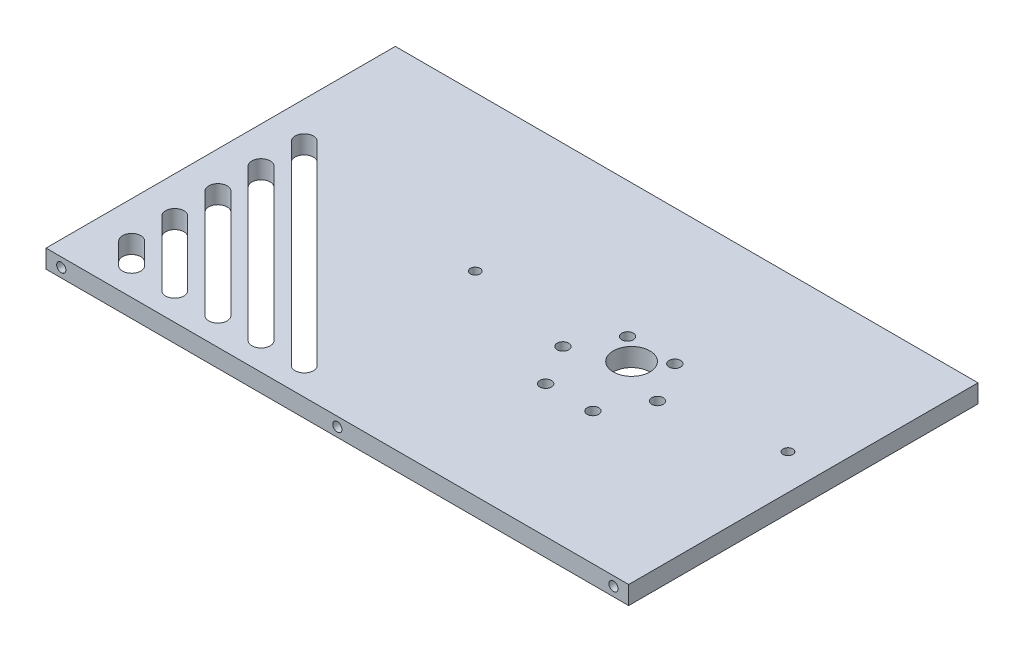
SolidWorks part; units mm, degrees
ref_plane "Front Plane" through (0, 0, 0) normal (1, 0, 0) x (0, 1, 0)
ref_plane "Top Plane" through (0, 0, 0) normal (0, 0, 1) x (0, 1, 0)
ref_plane "Right Plane" through (0, 0, 0) normal (0, 1, 0) x (-1, 0, 0)
sketch "Sketch1" plane through (0, 0, 0) normal (0, 1, 0) x (-1, 0, 0)
  line L3 (191, 0) -> (0, 0)
  line L10 (0, 114.5) -> (191, 114.5)
  line L15 (191, 114.5) -> (191, 0)
  line L17 (0, 114.5) -> (0, 0)
  point P16 (-5.5507, 58)
  point P19 (0, 0)
  point P27 (191, 0)
  dimension "D1" = 191
  dimension "D3" = 114.5
extrude "Boss-Extrude1" add sketch "Sketch1" along normal blind 6 contours L10 L17 L3 L15 region at (-95.5, 0, 57.25)
sketch "Sketch2" plane through (0, 0, 0) normal (0, -1, 0) x (1, 0, 0)
  line L0 (-113.4294, 6) -> (27.4505, 6) construction
  line L1 (-153.4835, 108.5) -> (20.1803, 108.5) construction
  line L2 (-48.0825, 39.2019) -> (29.2007, 39.2019) construction
  line L3 (-81.35, 53.663) -> (-81.35, 63.7746) construction
  line L4 (-191, 114.5) -> (-191, 0) construction
  line L7 (-44.35, 45.4394) -> (-44.35, 50045.4394) construction
  line L8 (-10, 10.8138) -> (-10, 44.7981) construction
  line L9 (-179, 84.2868) -> (-157.7868, 105.5) construction
  line L10 (-181.1213, 86.4081) -> (-159.9081, 107.6213)
  line L11 (-176.8787, 82.1655) -> (-155.6655, 103.3787)
  line L12 (-179, 70.1447) -> (-143.6447, 105.5) construction
  line L13 (-181.1213, 72.266) -> (-145.766, 107.6213)
  line L14 (-176.8787, 68.0233) -> (-141.5233, 103.3787)
  line L15 (-179, 56.0025) -> (-129.5025, 105.5) construction
  line L16 (-181.1213, 58.1238) -> (-131.6238, 107.6213)
  line L17 (-176.8787, 53.8812) -> (-127.3812, 103.3787)
  line L18 (-179, 41.8604) -> (-115.3604, 105.5) construction
  line L19 (-181.1213, 43.9817) -> (-117.4817, 107.6213)
  line L20 (-176.8787, 39.7391) -> (-113.2391, 103.3787)
  line L21 (-182, 120.5517) -> (-182, 16.1068) construction
  line L23 (-62.85, -5.1417) -> (-62.85, -109.5866) construction
  line L24 (-179, 98.4289) -> (-171.9289, 105.5) construction
  line L25 (-166.2721, 92.7721) -> (-163.4437, 89.9437) construction
  line L26 (-159.201, 85.701) -> (-156.3726, 82.8726) construction
  line L27 (-152.1299, 78.6299) -> (-149.3015, 75.8015) construction
  line L28 (-181.1213, 100.5503) -> (-174.0503, 107.6213)
  line L29 (-176.8787, 96.3076) -> (-169.8076, 103.3787)
  line L30 (-170.5147, 97.0147) -> (-173.3431, 99.8431) construction
  line L32 (-191, 0) -> (0, 0) construction
  line L33 (-62.85, 57.7019) -> (-62.85, -1.2686) construction
  line L35 (0, 114.5) -> (-191, 114.5) construction
  line L36 (0, 114.5) -> (0, 0) construction
  circle A7 centre (-62.85, 50.7019) radius 6
  circle A9 centre (-62.85, 57.7019) radius 18.5 construction
  arc A11 (-181.1213, 86.4081) -> (-176.8787, 82.1655) centre (-179, 84.2868) ccw
  arc A12 (-155.6655, 103.3787) -> (-159.9081, 107.6213) centre (-157.7868, 105.5) ccw
  arc A13 (-181.1213, 72.266) -> (-176.8787, 68.0233) centre (-179, 70.1447) ccw
  arc A14 (-141.5233, 103.3787) -> (-145.766, 107.6213) centre (-143.6447, 105.5) ccw
  arc A15 (-181.1213, 58.1238) -> (-176.8787, 53.8812) centre (-179, 56.0025) ccw
  arc A16 (-127.3812, 103.3787) -> (-131.6238, 107.6213) centre (-129.5025, 105.5) ccw
  arc A17 (-181.1213, 43.9817) -> (-176.8787, 39.7391) centre (-179, 41.8604) ccw
  arc A18 (-113.2391, 103.3787) -> (-117.4817, 107.6213) centre (-115.3604, 105.5) ccw
  arc A19 (-181.1213, 100.5503) -> (-176.8787, 96.3076) centre (-179, 98.4289) ccw
  arc A20 (-169.8076, 103.3787) -> (-174.0503, 107.6213) centre (-171.9289, 105.5) ccw
  circle A21 centre (-62.85, 57.7019) radius 15.5 construction
  circle A22 centre (-78.35, 57.7019) radius 1.9
  circle A23 centre (-70.6, 71.1253) radius 1.9
  circle A24 centre (-55.1, 71.1253) radius 1.9
  circle A25 centre (-47.35, 57.7019) radius 1.9
  circle A26 centre (-55.1, 44.2785) radius 1.9
  circle A27 centre (-70.6, 44.2785) radius 1.9
  circle A32 centre (-62.85, 50.7019) radius 51.25 construction
  circle A33 centre (-114.1, 50.7019) radius 1.6
  circle A34 centre (-62.85, 101.9519) radius 1.6 construction
  circle A35 centre (-11.6, 50.7019) radius 1.6
  circle A36 centre (-62.85, -0.5481) radius 1.6 construction
  point P24 (-175.4645, 101.9645)
  point P45 (-168.3934, 94.8934)
  point P50 (-161.3223, 87.8223)
  point P57 (-154.2513, 80.7513)
  point P64 (-147.1802, 73.6802)
  dimension "D14" = 31
  dimension "D15" = 3.8
  dimension "D2" = 37
  dimension "D6" = 12
  dimension "D3" = 102.5
  dimension "D9" = 3.2
  dimension "D7" = 45
  dimension "D8" = 6
  dimension "D11" = 4
  dimension "D13" = 7
  dimension "D5" = 6
  dimension "D10" = 6
  dimension "D4" = 33.2019
  dimension "D17" = 10
  dimension "D19" = 10
  dimension "D20" = 9
  dimension "D16" = 6
  dimension "D18" = 4
extrude "Cut-Extrude1" cut sketch "Sketch2" against normal up to next
sketch "Sketch3" plane through (0, 0, 0) normal (0, 0, -1) x (1, 0, 0)
  line L2 (0, -3) -> (50000, -3) construction
  line L3 (0, -6) -> (0, 0) construction
  line L4 (-191, -6) -> (-191, 0) construction
  line L5 (-95.5, 0) -> (-95.5, -6) construction
  line L6 (-191, 0) -> (0, 0) construction
  line L7 (-191, -6) -> (0, -6) construction
  circle A0 centre (-5, -3) radius 1.5
  circle A1 centre (-186, -3) radius 1.5
  circle A2 centre (-95.5, -3) radius 1.5
  point P11 (0, -3)
  dimension "D1" = 3
  dimension "D3" = 5
  dimension "D2" = 5
extrude "Cut-Extrude2" cut sketch "Sketch3" against normal blind 20
extrude "Cut-Extrude3" cut sketch "Sketch3<3>" along normal blind 20 from surface starting at face at (-95.5, 3, 114.5)
sketch "Sketch3<3>" plane through (0, 0, 0) normal (0, 0, -1) x (1, 0, 0) same geometry as "Sketch3"
equation "\"MotorDriverLength\"= 60mm"
equation "\"MotorLength\"= 60"
equation "\"MotorDriverWidth\"=45"
equation "\"MotorWidth\"= 37"
equation "\"InnerWallThickness\"=3"
equation "\"BatteryWidth\"= 60"
equation "\"OuterWallThickness\" = 6"
equation "\"CompartmentHeight\"=37"
equation "\"CompartmentWidth\"= \"MotorDriverLength\""
equation "\"MotorDiameter\"=37"
equation "\"BatteryHeight\"=24.2019"
equation "\"MotorDriverHeight\"=20"
equation "\"CircuitHeight\"=30"
equation "\"FanThickness\"= 10"
equation "\"FanHeight\"=50"
equation "\"D1@Boss-Extrude1\" = \"OuterWallThickness\""
equation "\"MotorShaftHole\"=12"
equation "\"BearingBore\"=4"
equation "\"MinShinWidth\"= 20"
equation "\"ShinThickness\"=10"
equation "\"PivotDistance\"=40"
equation "\"ThighLength\"= 200"
equation "\"HipBore\"=27"
equation "\"ThighThickness\"=20"
equation "\"MaxBending\"=135"
equation "\"MaxStretchingAngle\"= 140"
equation "\"ThighJointDistance\"=157.485"
equation "\"ShinLength\"=100"
equation "\"BearingDiameter\"= 10"
equation "\"D2@Sketch2\"=\"MotorDiameter\""
equation "\"D6@Sketch2\"=\"MotorShaftHole\""
equation "\"D5@Sketch2\"=\"OuterWallThickness\""
equation "\"D10@Sketch2\"=\"OuterWallThickness\""
equation "\"D4@Sketch2\"=\"BatteryHeight\"+\"OuterWallThickness\"+\"InnerWallThickness\""
equation "\"GearboxDiameter\"=102.5"
equation "\"D1@Sketch1\" = \"ChessisInnerWidth\""
equation "\"ChessisInnerWidth\"= \"OuterWallThickness\" * 2 + \"MotorDriverLength\" * 2 + \"InnerWallThickness\" * 3 + \"CircuitLength\""
equation "\"CircuitLength\"=50"
equation "\"D3@Sketch1\"=\"GearboxDiameter\"+\"OuterWallThickness\"*2"
equation "\"D3@Sketch2\"=\"GearboxDiameter\""
equation "\"D17@Sketch2\"=\"OuterWallThickness\"+4"
equation "\"D20@Sketch2\"=\"OuterWallThickness\"+3"
